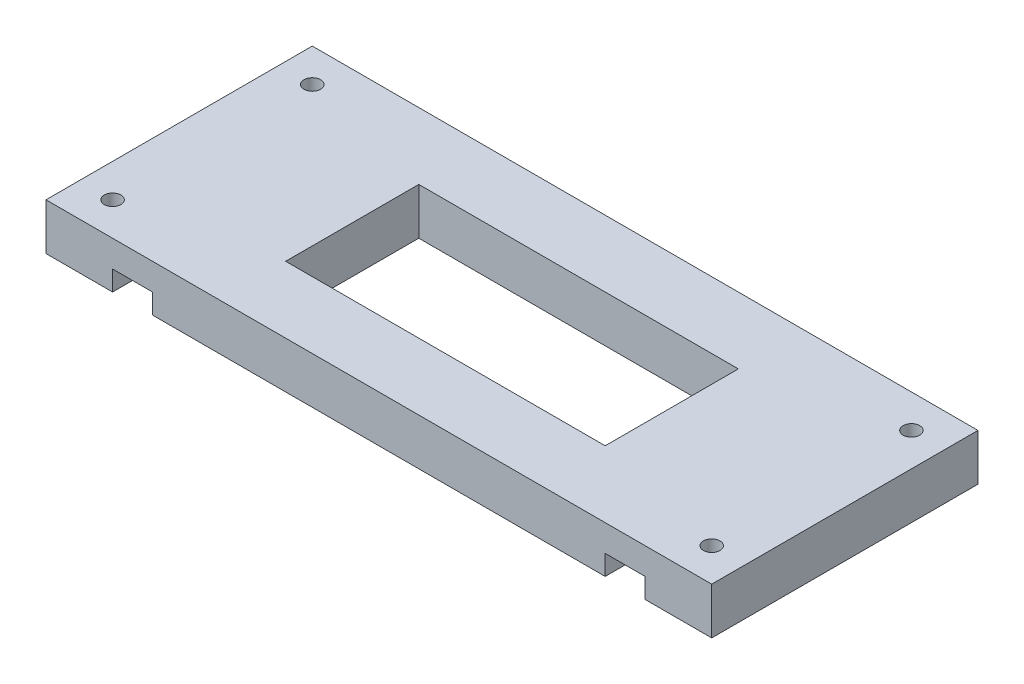
SolidWorks part; units mm, degrees
ref_plane "Plan de face" through (0, 0, 0) normal (0, 0, 1) x (1, 0, 0)
ref_plane "Plan de dessus" through (0, 0, 0) normal (0, 1, 0) x (1, 0, 0)
ref_plane "Plan de droite" through (0, 0, 0) normal (1, 0, 0) x (0, 0, -1)
sketch "Esquisse1" plane through (0, 0, 0) normal (0, 0, 1) x (1, 0, 0)
  line L0 (0, 0) -> (10, 0)
  line L1 (0, 7) -> (100, 7)
  line L2 (0, 7) -> (0, 0)
  line L3 (100, 7) -> (100, 0)
  line L4 (10, 0) -> (10, 3)
  line L5 (10, 3) -> (16, 3)
  line L6 (16, 3) -> (16, 0)
  line L7 (16, 0) -> (84, 0)
  line L8 (84, 0) -> (84, 3)
  line L9 (84, 3) -> (90, 3)
  line L10 (90, 3) -> (90, 0)
  line L11 (90, 0) -> (100, 0)
  dimension "D1" = 7
  dimension "D2" = 100
  dimension "D3" = 3
  dimension "D4" = 6
  dimension "D5" = 10
extrude "Boss.-Extru.1" add sketch "Esquisse1" along normal blind 40
sketch "Esquisse2" plane through (0, 7, 0) normal (0, 1, 0) x (1, 0, 0)
  line L1 (26, -10) -> (74, -10)
  line L2 (26, -10) -> (26, -30)
  line L3 (26, -30) -> (74, -30)
  line L4 (74, -10) -> (74, -30)
  line L5 (16, -40) -> (16, 0) construction
  line L6 (16, -40) -> (84, -40) construction
  line L7 (16, -40) -> (16, 0) construction
  line L8 (16, -40) -> (84, -40) construction
  point P8 (26, -20)
  point P9 (16, -20)
  point P10 (50, -40)
  point P11 (50, -30)
  dimension "D1" = 10
  dimension "D2" = 10
extrude "Enlèv. mat.-Extru.1" cut sketch "Esquisse2" against normal up to next
sketch "Esquisse3" plane through (0, 0, 0) normal (0, -1, 0) x (1, 0, 0)
  line L0 (0, 40) -> (10, 40) construction
  line L1 (90, 40) -> (100, 40) construction
  line L2 (5, 35) -> (5, 5) construction
  line L3 (0, 40) -> (0, 0) construction
  circle A0 centre (5, 35) radius 1.25
  circle A1 centre (5, 5) radius 1.25
  circle A2 centre (95, 35) radius 1.25
  circle A3 centre (95, 5) radius 1.25
  point P8 (5, 20)
  point P11 (5, 40)
  point P14 (0, 20)
  point P17 (95, 40)
  dimension "D2" = 2.5
  dimension "D1" = 30
extrude "Enlèv. mat.-Extru.2" cut sketch "Esquisse3" against normal up to next
